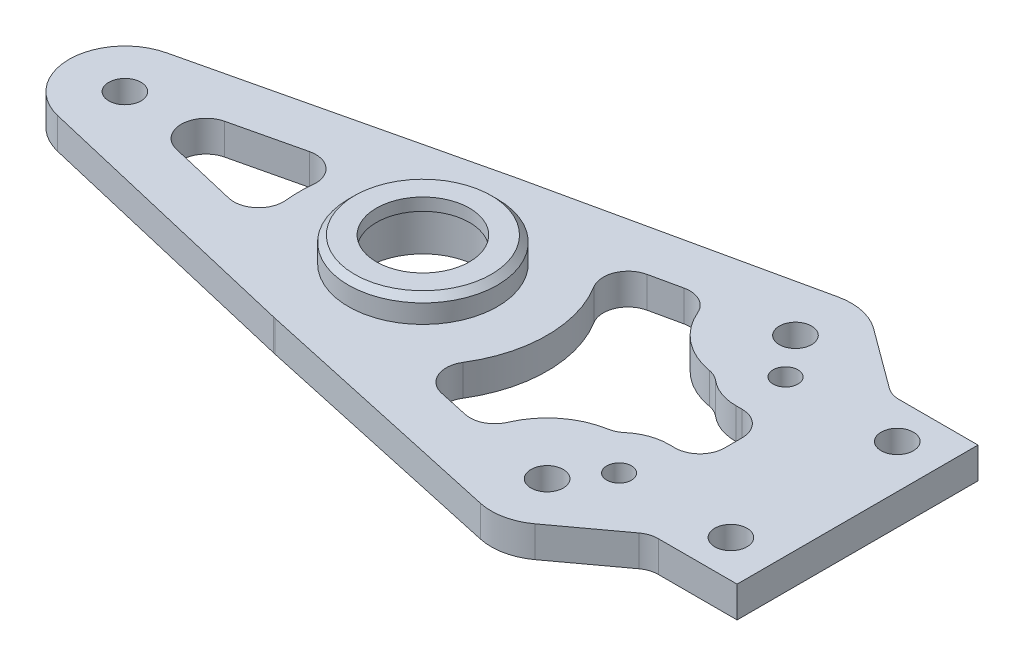
SolidWorks part; units mm, degrees
ref_plane "Front Plane" through (0, 0, 0) normal (0, 0, 1) x (1, 0, 0)
ref_plane "Top Plane" through (0, 0, 0) normal (0, 1, 0) x (1, 0, 0)
ref_plane "Right Plane" through (0, 0, 0) normal (1, 0, 0) x (0, 0, -1)
sketch "Sketch1" plane through (0, 0, 0) normal (0, 1, 0) x (1, 0, 0)
  line L0 (35, 9.7) -> (35, -9.7)
  line L1 (35, 9.7) -> (28.6566, 9.7)
  line L2 (35, -9.7) -> (28.6566, -9.7)
  line L3 (7.5892, 0) -> (-24.2432, 0) construction
  line L4 (22.5919, 5) -> (-33.5892, 5) construction
  line L5 (22.5919, -5) -> (-33.5892, -5) construction
  line L6 (28, 29.9214) -> (28, -27.3936) construction
  line L7 (-21, 30.6326) -> (-21, -25.3784) construction
  line L8 (31, 30.8205) -> (31, -25.1937) construction
  line L9 (0, 34.0703) -> (0, -31.8389) construction
  line L10 (-25.0312, 4.3802) -> (-2.2917, 9.7339)
  line L11 (-2.1347, 9.7695) -> (19.0394, 14.3963)
  line L12 (-25.0312, -4.3802) -> (-2.2917, -9.7339)
  line L13 (-2.1347, -9.7695) -> (19.0394, -14.3963)
  line L14 (22.6672, 13.6244) -> (27.4712, 10.0892)
  line L15 (22.6672, -13.6244) -> (27.4712, -10.0892)
  line L16 (9.7721, 8.2769) -> (12.2163, 8.811)
  line L17 (-17.9129, -1.9468) -> (-12.3876, -3.2476)
  line L18 (-17.9129, 1.9468) -> (-12.3876, 3.2476)
  line L20 (25, 0.7) -> (25, -0.7)
  line L21 (22.5, 2.7) -> (23, 2.7)
  line L22 (22.5, -2.7) -> (23, -2.7)
  line L25 (9.7721, -8.2769) -> (12.2163, -8.811)
  circle A0 centre (31.5, 6.7) radius 1.3
  circle A1 centre (31.5, -6.7) radius 1.3
  circle A2 centre (0, 0) radius 12 construction
  circle A3 centre (0, 0) radius 13.5 construction
  circle A4 centre (20, 10) radius 5 construction
  circle A5 centre (20, -10) radius 5 construction
  circle A6 centre (20, 10) radius 6.5 construction
  circle A7 centre (20, -10) radius 6.5 construction
  circle A8 centre (20, 10) radius 1.3
  circle A9 centre (20, -10) radius 1.3
  circle A10 centre (0, 0) radius 4.5
  circle A11 centre (-24, 0) radius 1.3
  circle A12 centre (22.5, -6.7) radius 1
  arc A13 (22.6672, 13.6244) -> (19.0394, 14.3963) centre (20, 10) ccw
  arc A14 (19.0394, -14.3963) -> (22.6672, -13.6244) centre (20, -10) ccw
  arc A15 (-2.1347, 9.7695) -> (-2.2917, 9.7339) centre (0, 0) ccw
  arc A16 (-25.0312, 4.3802) -> (-25.0312, -4.3802) centre (-24, 0) ccw
  arc A17 (28.6566, -9.7) -> (27.4712, -10.0892) centre (28.6566, -11.7) ccw
  arc A18 (28.6566, 9.7) -> (27.4712, 10.0892) centre (28.6566, 11.7) cw
  arc A19 (-2.2917, -9.7339) -> (-2.1347, -9.7695) centre (0, 0) ccw
  arc A20 (8.4992, 5.2692) -> (8.4992, -5.2691) centre (0, 0) cw
  arc A21 (14.4824, 7.6428) -> (18.9688, 4.0893) centre (20, 10) ccw
  arc A22 (18.9688, -4.0893) -> (14.4824, -7.6428) centre (20, -10) ccw
  arc A23 (-17.9129, -1.9468) -> (-17.9129, 1.9468) centre (-17.4545, 0) cw
  arc A24 (-9.9411, -1.084) -> (-9.9411, 1.084) centre (0, 0) cw
  arc A25 (22.5, -2.7) -> (19.9167, -3.646) centre (22.5, -6.7) ccw
  circle A26 centre (22.5, 6.7) radius 1
  arc A27 (14.4824, -7.6428) -> (12.2163, -8.811) centre (12.6432, -6.8571) cw
  arc A28 (19.9167, 3.646) -> (22.5, 2.7) centre (22.5, 6.7) ccw
  arc A29 (18.9688, -4.0893) -> (19.9167, -3.646) centre (18.6251, -2.119) ccw
  arc A30 (23, -2.7) -> (25, -0.7) centre (23, -0.7) ccw
  arc A31 (23, 2.7) -> (25, 0.7) centre (23, 0.7) cw
  arc A32 (18.9688, 4.0893) -> (19.9167, 3.646) centre (18.6251, 2.119) cw
  arc A33 (12.2163, 8.811) -> (14.4824, 7.6428) centre (12.6432, 6.8571) cw
  arc A34 (9.7721, 8.2769) -> (8.4992, 5.2692) centre (10.199, 6.323) ccw
  arc A35 (8.4992, -5.2691) -> (9.7721, -8.2769) centre (10.199, -6.323) ccw
  arc A36 (-9.9411, -1.084) -> (-12.3876, -3.2476) centre (-11.9293, -1.3008) cw
  arc A37 (-9.9411, 1.084) -> (-12.3876, 3.2476) centre (-11.9293, 1.3008) ccw
  point P27 (0, 0)
  point P28 (20, 10)
  point P29 (20, -10)
  point P45 (28, -9.7)
  point P58 (28, 9.7)
  dimension "D1" = 2.6
  dimension "D2" = 2.6
  dimension "D8" = 7
  dimension "D11" = 5
  dimension "D14" = 20
  dimension "D15" = 20
  dimension "D16" = 2.6
  dimension "D17" = 2.6
  dimension "D18" = 2.6
  dimension "D19" = 9
  dimension "D23" = 2
  dimension "D25" = 9
  dimension "D26" = 9
  dimension "D27" = 20
  dimension "D28" = 9
  dimension "D29" = 2
  dimension "D30" = 10
  dimension "D33" = 6
  dimension "D42" = 6
  dimension "D34" = 4
  dimension "D36" = 2
  dimension "D37" = 10
  dimension "D44" = 3
  dimension "D31" = 4
  dimension "D43" = 4
  dimension "D47" = 2
  dimension "D48" = 2
  dimension "D3" = 13.4
  dimension "D4" = 3.5
  dimension "D5" = 3.5
  dimension "D6" = 3
  dimension "D7" = 3
  dimension "D9" = 7
  dimension "D10" = 9.7
  dimension "D12" = 5
  dimension "D13" = 28
  dimension "D20" = 24
  dimension "D21" = 31
  dimension "D22" = 21
  dimension "D24" = 9
  dimension "D32" = 3
  dimension "D35" = 4
  dimension "D38" = 4
  dimension "D39" = 4
  dimension "D40" = 20
  dimension "D41" = 10
  dimension "D45" = 3
  dimension "D46" = 9
extrude "Boss-Extrude1" add sketch "Sketch1" along normal blind 2.5
cosmetic thread "Cosmetic Thread1" parameters "D2"=2.5
cosmetic thread "Cosmetic Thread2" parameters "D2"=2.5
ref_axis "Axis1" through (0, 11.4389, 0) along (0, -1, 0)
sketch "Sketch3" plane through (0, 2.5, 0) normal (0, 1, 0) x (1, 0, 0)
  circle A0 centre (0, 0) radius 3.75
  circle A1 centre (0, 0) radius 6
  dimension "D1" = 7.5
  dimension "D2" = 12
extrude "Boss-Extrude2" add sketch "Sketch3" along normal blind 2
sketch "Sketch4" plane through (0, 2.5, 0) normal (0, -1, 0) x (1, 0, 0)
  circle A0 centre (0, 0) radius 3.75
  circle A1 centre (0, 0) radius 4.5
extrude "Cut-Extrude1" cut sketch "Sketch4" against normal blind 1
chamfer "Chamfer1" distance 0.5 angle 45 1 edges at (0, 4.5, 6)
